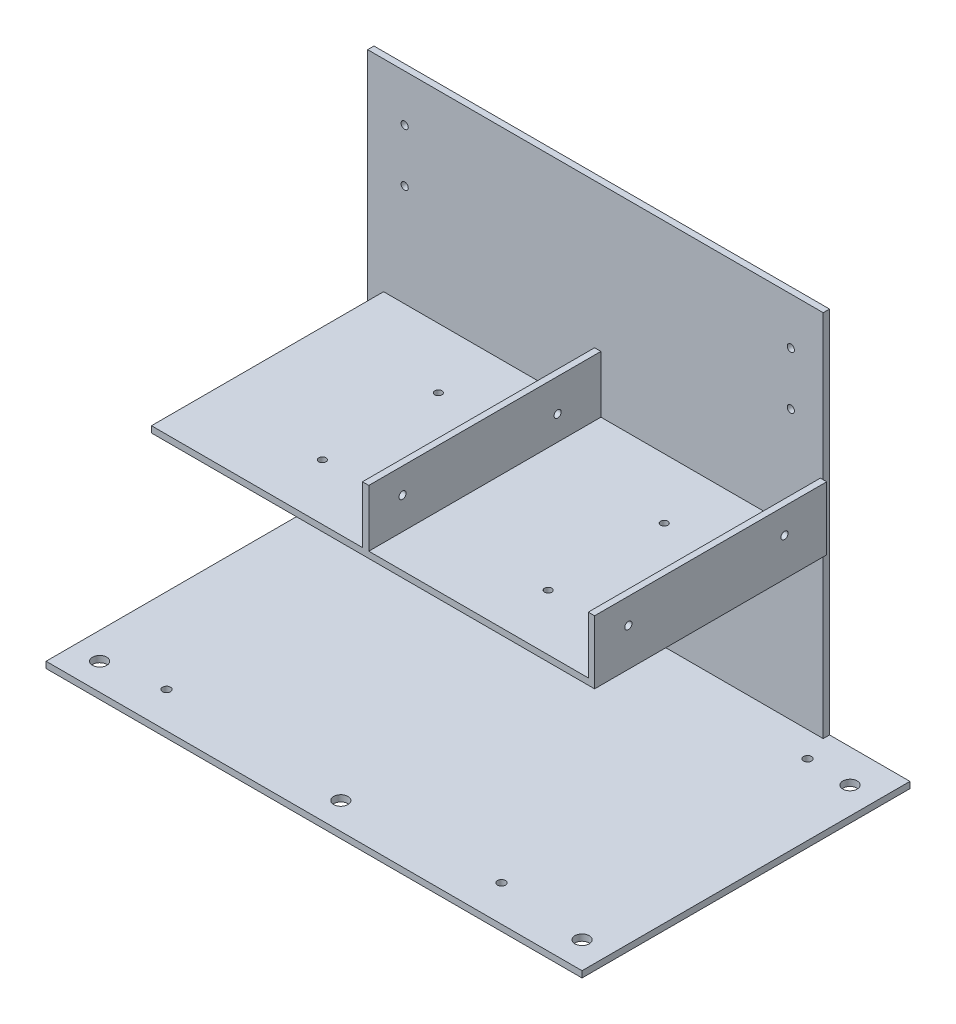
SolidWorks part; units mm, degrees
ref_plane "Front Plane" through (0, 0, 0) normal (0, 0, 1) x (1, 0, 0)
ref_plane "Top Plane" through (0, 0, 0) normal (0, 1, 0) x (1, 0, 0)
ref_plane "Right Plane" through (0, 0, 0) normal (1, 0, 0) x (0, 0, -1)
sketch "Sketch1" plane through (0, 0, 0) normal (0, 1, 0) x (1, 0, 0)
  line L1 (0, 0) -> (254, 0)
  line L2 (0, 0) -> (0, -152.4)
  line L3 (0, -152.4) -> (254, -152.4)
  line L4 (254, 0) -> (254, -152.4)
  dimension "D1" = 254
  dimension "D2" = 152.4
extrude "Boss-Extrude1" add sketch "Sketch1" along normal blind 3
sketch "Sketch2" plane through (0, 0, 0) normal (0, 0, -1) x (-1, 0, 0)
  line L1 (-254, 0) -> (0, 0)
  line L2 (-254, 0) -> (-254, 177.8)
  line L3 (-254, 177.8) -> (0, 177.8)
  line L4 (0, 0) -> (0, 177.8)
  dimension "D1" = 177.8
extrude "Boss-Extrude2" add sketch "Sketch2" along normal blind 3
sketch "Sketch3" plane through (0, 0, 0) normal (0, 0, 1) x (1, 0, 0)
  line L0 (10.5531, 90.7404) -> (10.5531, 110.8404) construction
  line L1 (7.5531, 109.2404) -> (217.5531, 109.2404)
  line L2 (7.5531, 109.2404) -> (7.5531, 79.2404)
  line L3 (7.5531, 79.2404) -> (217.5531, 79.2404)
  line L4 (217.5531, 109.2404) -> (217.5531, 79.2404)
  line L8 (158.2531, 82.2404) -> (213.1531, 82.2404) construction
  line L9 (214.5531, 83.6404) -> (214.5531, 110.8404) construction
  dimension "D1" = 3
  dimension "D2" = 3
  dimension "D3" = 3
  dimension "D4" = 30
extrude "Boss-Extrude3" add sketch "Sketch3" along normal blind 110
sketch "Sketch4" plane through (0, 0, 110) normal (0, 0, 1) x (1, 0, 0)
  line L0 (217.5531, 109.2404) -> (7.5531, 109.2404) construction
  line L1 (214.5531, 82.2404) -> (110.5531, 82.2404)
  line L2 (214.5531, 82.2404) -> (214.5531, 109.2404)
  line L3 (214.5531, 109.2404) -> (110.5531, 109.2404)
  line L4 (110.5531, 82.2404) -> (110.5531, 109.2404)
  line L5 (217.5531, 79.2404) -> (217.5531, 109.2404) construction
  line L6 (107.5531, 82.2404) -> (7.5531, 82.2404)
  line L7 (107.5531, 82.2404) -> (107.5531, 109.2404)
  line L8 (107.5531, 109.2404) -> (7.5531, 109.2404)
  line L9 (7.5531, 82.2404) -> (7.5531, 109.2404)
  line L10 (7.5531, 79.2404) -> (217.5531, 79.2404) construction
  line L11 (7.5531, 79.2404) -> (217.5531, 79.2404) construction
  line L12 (107.5531, 83.6404) -> (107.5531, 110.8404) construction
  line L13 (7.5531, 109.2404) -> (7.5531, 79.2404) construction
  line L14 (217.5531, 109.2404) -> (7.5531, 109.2404) construction
  dimension "D1" = 3
  dimension "D2" = 3
  dimension "D3" = 3
  dimension "D4" = 3
  dimension "D5" = 3
extrude "Cut-Extrude1" cut sketch "Sketch4" against normal blind 110
hole_wizard "#6 Clearance Hole1" positions "Sketch8" profile "Sketch9" hole size "#6" standard "ANSI Inch" end condition up to next
sketch "Sketch8" plane through (0, 0, 0) normal (0, -1, 0) x (-1, 0, 0)
  point P0 (-40.113, -11.985)
  point P4 (-40.113, -135.429)
  point P7 (-220.453, -11.985)
  point P10 (-198.863, -135.429)
sketch "Sketch9" plane through (40.113, 0, 11.985) normal (1, 0, 0) x (0, 0, -1)
  line L0 (0, 0) -> (0, 3)
  line L1 (0, 3) -> (1.8986, 3)
  line L2 (1.8986, 3) -> (1.8986, 0)
  line L5 (1.8986, 0) -> (0, 0)
  line L11 (0, -6.35) -> (0, 107.95) construction
  dimension "Thru Hole Dia." = 3.7973
  dimension "Thru Hole Depth" = 3
hole_wizard "M3 Clearance Hole1" positions "Sketch12" profile "Sketch13" hole size "M3" standard "ANSI Metric" end condition up to next
sketch "Sketch12" plane through (0, 79.2404, 0) normal (0, -1, 0) x (-1, 0, 0)
  point P0 (-62.0531, -28.5)
  point P3 (-62.0531, -83.5)
  point P6 (-169.0531, -83.5)
  point P9 (-169.0531, -28.5)
sketch "Sketch13" plane through (62.0531, 79.2404, 28.5) normal (1, 0, 0) x (0, 0, -1)
  line L0 (0, 0) -> (0, 3)
  line L1 (0, 3) -> (1.7, 3)
  line L2 (1.7, 3) -> (1.7, 0)
  line L5 (1.7, 0) -> (0, 0)
  line L11 (0, -6.35) -> (0, 107.95) construction
  dimension "Thru Hole Dia." = 3.4
  dimension "Thru Hole Depth" = 3
hole_wizard "M3 Clearance Hole2" positions "Sketch14" profile "Sketch15" hole size "M3" standard "ANSI Metric" end condition up to next
sketch "Sketch14" plane through (110.5531, 0, 0) normal (1, 0, 0) x (0, 0, -1)
  point P0 (-94, 97.2404)
  point P3 (-20.5069, 93.8291)
sketch "Sketch15" plane through (110.5531, 97.2404, 94) normal (0, 1, 0) x (0, 0, -1)
  line L0 (0, 0) -> (0, 3)
  line L1 (0, 3) -> (1.7, 3)
  line L2 (1.7, 3) -> (1.7, 0)
  line L5 (1.7, 0) -> (0, 0)
  line L11 (0, -6.35) -> (0, 107.95) construction
  dimension "Thru Hole Dia." = 3.4
  dimension "Thru Hole Depth" = 3
hole_wizard "M3 Clearance Hole3" positions "Sketch18" profile "Sketch19" hole size "M3" standard "ANSI Metric" end condition up to next
sketch "Sketch18" plane through (217.5531, 0, 0) normal (1, 0, 0) x (0, 0, -1)
  point P0 (-94, 97.2404)
  point P3 (-20, 97.2404)
sketch "Sketch19" plane through (217.5531, 97.2404, 94) normal (0, 1, 0) x (0, 0, -1)
  line L0 (0, 0) -> (0, 3)
  line L1 (0, 3) -> (1.7, 3)
  line L2 (1.7, 3) -> (1.7, 0)
  line L5 (1.7, 0) -> (0, 0)
  line L11 (0, -6.35) -> (0, 107.95) construction
  dimension "Thru Hole Dia." = 3.4
  dimension "Thru Hole Depth" = 3
hole_wizard "1/4 Clearance Hole1" positions "Sketch22" profile "Sketch23" hole size "1/4" standard "ANSI Inch" end condition up to next
sketch "Sketch22" plane through (0, 3, 0) normal (0, 1, 0) x (1, 0, 0)
  line L13 (254, -139.7) -> (0, -139.7) construction
  line L15 (254, -76.2) -> (0, -76.2) construction
  line L16 (254, -152.4) -> (254, 0) construction
  line L17 (0, 0) -> (0, -152.4) construction
  line L21 (0, -152.4) -> (254, -152.4) construction
  line L23 (127, -152.4) -> (127, 0) construction
  line L24 (254, 0) -> (0, 0) construction
  point P93 (241.3, -139.7)
  point P96 (12.7, -139.7)
  point P98 (12.7, -12.7)
  point P99 (241.3, -12.7)
  point P100 (127, -139.7)
  point P102 (244.4898, -272.9773)
  dimension "D1" = 114.3
  dimension "D2" = 12.7
sketch "Sketch23" plane through (244.4898, 3, 272.9773) normal (1, 0, 0) x (0, 0, 1)
  line L0 (0, 0) -> (0, 3)
  line L1 (0, 3) -> (3.3782, 3)
  line L2 (3.3782, 3) -> (3.3782, 0)
  line L5 (3.3782, 0) -> (0, 0)
  line L11 (0, -6.35) -> (0, 107.95) construction
  dimension "Thru Hole Dia." = 6.7564
  dimension "Thru Hole Depth" = 3
hole_wizard "M3 Clearance Hole4" positions "Sketch24" profile "Sketch25" hole size "M3" standard "ANSI Metric" end condition up to next
sketch "Sketch24" plane through (0, 0, 0) normal (0, 0, 1) x (1, 0, 0)
  point P0 (17.5531, 155.5904)
  point P3 (17.5531, 130.5904)
  point P6 (200.5531, 155.5904)
  point P9 (200.5531, 130.5904)
sketch "Sketch25" plane through (17.5531, 155.5904, 0) normal (1, 0, 0) x (0, -1, 0)
  line L0 (0, 0) -> (0, 3)
  line L1 (0, 3) -> (1.7, 3)
  line L2 (1.7, 3) -> (1.7, 0)
  line L5 (1.7, 0) -> (0, 0)
  line L11 (0, -6.35) -> (0, 107.95) construction
  dimension "Thru Hole Dia." = 3.4
  dimension "Thru Hole Depth" = 3
sketch "Sketch26" plane through (0, 0, 0) normal (0, 0, 1) x (1, 0, 0)
  line L2 (215.9, 3) -> (215.9, 177.8)
  line L7 (254, 3) -> (0, 3) construction
  line L8 (0, 177.8) -> (254, 177.8) construction
  line L9 (215.9, 177.8) -> (254, 177.8)
  line L10 (254, 177.8) -> (254, 3)
  line L11 (254, 3) -> (215.9, 3)
  dimension "D1" = 38.1
extrude "Cut-Extrude2" cut sketch "Sketch26" against normal up to next
ref_axis "Axis1" through (241.3, 0, 139.7) along (0, 1, 0)
ref_axis "Axis2" through (12.7, 0, 139.7) along (0, 1, 0)
